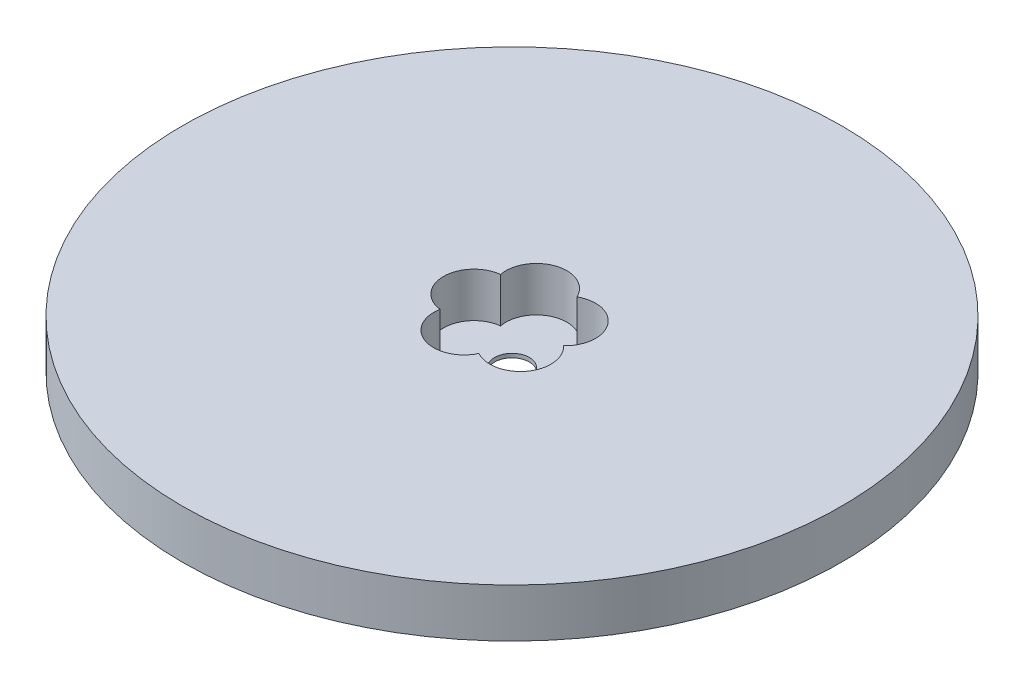
SolidWorks part; units mm, degrees
ref_plane "Front Plane" through (0, 0, 0) normal (0, 0, 1) x (1, 0, 0)
ref_plane "Top Plane" through (0, 0, 0) normal (0, 1, 0) x (1, 0, 0)
ref_plane "Right Plane" through (0, 0, 0) normal (1, 0, 0) x (0, 0, -1)
sketch "Sketch1" plane through (0, 0, 0) normal (0, 1, 0) x (1, 0, 0)
  circle A0 centre (0, 0) radius 95
  dimension "FLANGE_OD" = 190
extrude "Boss-Extrude1" add sketch "Sketch1" along normal blind 14
sketch "Sketch2" plane through (0, 0, 0) normal (0, 1, 0) x (1, 0, 0)
  circle A0 centre (0, 0) radius 5
  dimension "BORE_D" = 10
extrude "Cut-Extrude1" cut sketch "Sketch2" along normal through all
sketch "Sketch3" plane through (0, 14, 0) normal (0, 1, 0) x (1, 0, 0)
  circle A0 centre (0, 0) radius 10.9535 construction
  circle A1 centre (-10.9535, 0) radius 8.7971
  dimension "BOLT_D" = 17.5943
  dimension "BOLT_PCD" = 21.907
extrude "Cut-Extrude2" cut sketch "Sketch3" against normal blind 12.856
pattern_circular "CirPattern1" count 5 over 360 about axis through (0, 0, 0) along (0, 1, 0) of "Cut-Extrude2"
